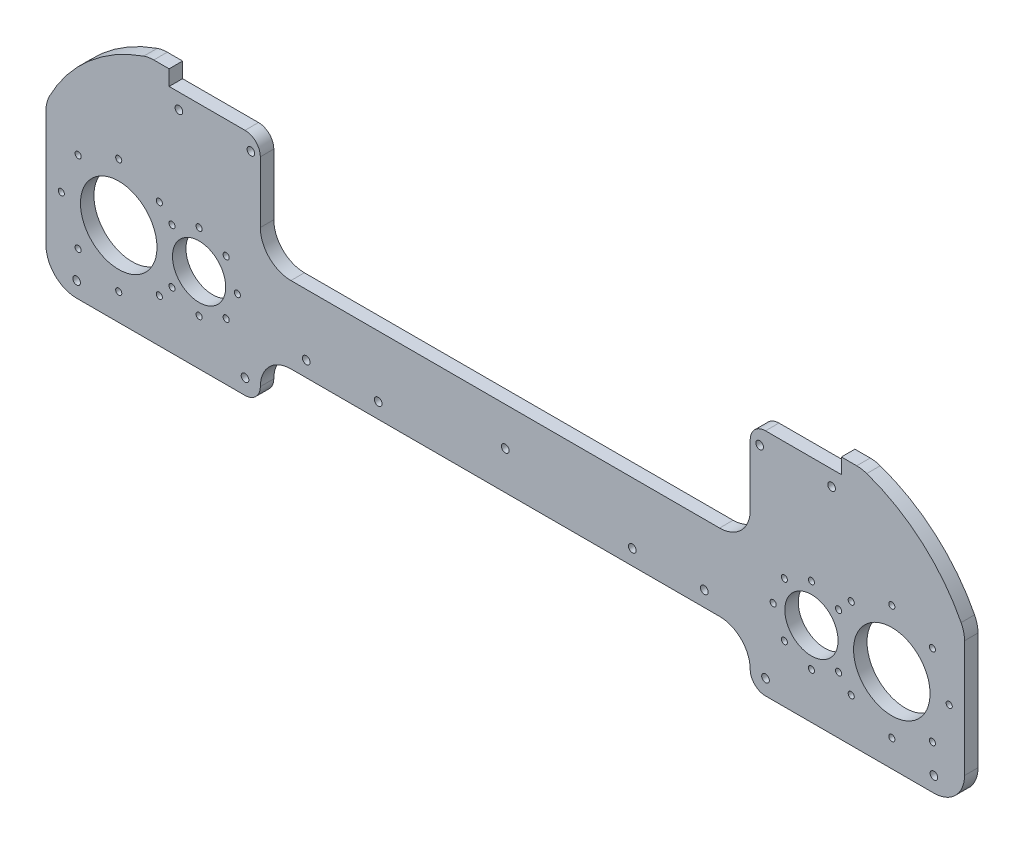
SolidWorks part; units mm, degrees
material "ABS"
ref_plane "Front Plane" through (0, 0, 0) normal (0, 0, 1) x (1, 0, 0)
ref_plane "Top Plane" through (0, 0, 0) normal (0, 1, 0) x (1, 0, 0)
ref_plane "Right Plane" through (0, 0, 0) normal (1, 0, 0) x (0, 0, -1)
sketch "Sketch1" plane through (0, 0, 0) normal (0, 0, 1) x (1, 0, 0)
  line L0 (-145.7836, 66.675) -> (145.7836, 66.675)
  line L1 (-190.5, 26.1817) -> (-190.5, -22.225)
  line L4 (0, 0) -> (0, 100.7987) construction
  line L5 (-177.8, -34.925) -> (177.8, -34.925)
  line L6 (190.5, 26.1817) -> (190.5, -22.225)
  line L7 (-190.5, 34.925) -> (190.5, -34.925) construction
  line L8 (-190.5, -34.925) -> (190.5, 34.925) construction
  arc A0 (177.8, -34.925) -> (190.5, -22.225) centre (177.8, -22.225) ccw
  arc A1 (149.9577, 65.9694) -> (189.0889, 31.9999) centre (127, 0) cw
  circle A2 centre (-127, 0) radius 3.175
  circle A3 centre (127, 0) radius 3.175
  arc A4 (-177.8, -34.925) -> (-190.5, -22.225) centre (-177.8, -22.225) cw
  arc A5 (190.5, 26.1817) -> (189.0889, 31.9999) centre (177.8, 26.1817) ccw
  arc A6 (-149.9577, 65.9694) -> (-189.0889, 31.9999) centre (-127, 0) ccw
  arc A7 (149.9577, 65.9694) -> (145.7836, 66.675) centre (145.7836, 53.975) ccw
  arc A8 (-190.5, 26.1817) -> (-189.0889, 31.9999) centre (-177.8, 26.1817) cw
  arc A9 (-145.7836, 66.675) -> (-149.9577, 65.9694) centre (-145.7836, 53.975) ccw
  point P0 (0, 0)
  point P22 (190.5, 29.0994)
  point P27 (147.8199, 66.675)
  point P30 (-190.5, 29.0994)
  point P33 (-147.8199, 66.675)
  dimension "D3" = 6.35
  dimension "D4" = 6.35
  dimension "D6" = 66.675
  dimension "D7" = 12.7
  dimension "D2" = 381
  dimension "D5" = 12.7
  dimension "D1" = 69.85
  dimension "D8" = 139.7
extrude "Boss-Extrude1" add sketch "Sketch1" along normal mid plane 5.588
sketch "Sketch2" plane through (0, 0, 2.794) normal (0, 0, 1) x (1, 0, 0)
  line L0 (-127, 0) -> (-207.737, 0) construction
  line L1 (127, 0) -> (207.737, 0) construction
  line L4 (0, 0) -> (0, 93.9723) construction
  circle A0 centre (-127, 0) radius 11.049
  circle A1 centre (-160.3375, 0) radius 15.875
  circle A2 centre (-143.4995, 16.838) radius 1.27
  circle A3 centre (-136.525, 0) radius 1.27 [skipped]
  circle A4 centre (-160.3375, 0) radius 23.8125 construction
  circle A5 centre (-127, 0) radius 15.875 construction
  circle A6 centre (-160.3375, 23.8125) radius 1.27
  circle A7 centre (-143.4995, -16.838) radius 1.27
  circle A8 centre (-160.3375, -23.8125) radius 1.27
  circle A9 centre (-177.1755, -16.838) radius 1.27
  circle A10 centre (-184.15, 0) radius 1.27
  circle A11 centre (-177.1755, 16.838) radius 1.27
  circle A12 centre (127, 0) radius 15.875 construction
  circle A13 centre (160.3375, 0) radius 23.8125 construction
  circle A14 centre (-127, 15.875) radius 1.27
  circle A15 centre (-115.7747, 11.2253) radius 1.27
  circle A16 centre (-111.125, 0) radius 1.27
  circle A17 centre (-115.7747, -11.2253) radius 1.27
  circle A18 centre (-127, -15.875) radius 1.27
  circle A19 centre (-138.2253, -11.2253) radius 1.27
  circle A20 centre (138.2253, 11.2253) radius 1.27
  circle A21 centre (-138.2253, 11.2253) radius 1.27
  circle A22 centre (-142.875, 0) radius 1.27 [skipped]
  circle A23 centre (138.2253, -11.2253) radius 1.27
  circle A24 centre (127, -15.875) radius 1.27
  circle A25 centre (115.7747, -11.2253) radius 1.27
  circle A26 centre (111.125, 0) radius 1.27
  circle A27 centre (115.7747, 11.2253) radius 1.27
  circle A28 centre (127, 15.875) radius 1.27
  circle A29 centre (177.1755, 16.838) radius 1.27
  circle A30 centre (184.15, 0) radius 1.27
  circle A31 centre (177.1755, -16.838) radius 1.27
  circle A32 centre (160.3375, -23.8125) radius 1.27
  circle A33 centre (143.4995, -16.838) radius 1.27
  circle A34 centre (160.3375, 23.8125) radius 1.27
  circle A35 centre (143.4995, 16.838) radius 1.27
  circle A36 centre (160.3375, 0) radius 15.875
  circle A37 centre (127, 0) radius 11.049
  dimension "D2" = 33.3375
  dimension "D3" = 31.75
  dimension "D4" = 31.75
  dimension "D5" = 47.625
  dimension "D6" = 2.54
  dimension "D1" = 22.098
  dimension "D8" = 2.54
  dimension "D7" = 8
  dimension "D9" = 8
extrude "Cut-Extrude1" cut sketch "Sketch2" against normal through all
sketch "Sketch5" plane through (0, 0, 2.794) normal (0, 0, 1) x (1, 0, 0)
  line L0 (145.7836, 66.675) -> (-145.7836, 66.675) construction
  line L1 (-88.9, 15.875) -> (88.9, 15.875)
  line L2 (-101.6, 28.575) -> (-101.6, 66.675)
  line L3 (-101.6, 66.675) -> (101.6, 66.675)
  line L4 (101.6, 28.575) -> (101.6, 66.675)
  line L5 (-101.6, 15.875) -> (101.6, 66.675) construction
  line L6 (-101.6, 66.675) -> (101.6, 15.875) construction
  line L7 (0, 0) -> (0, 128.2224) construction
  arc A0 (101.6, 28.575) -> (88.9, 15.875) centre (88.9, 28.575) cw
  arc A1 (-88.9, 15.875) -> (-101.6, 28.575) centre (-88.9, 28.575) cw
  point P0 (0, 41.275)
  dimension "D3" = 12.7
  dimension "D1" = 50.8
  dimension "D2" = 203.2
extrude "ITC_Cutout" cut sketch "Sketch5" against normal through all
sketch "Sketch6" plane through (0, 0, 2.794) normal (0, 0, 1) x (1, 0, 0)
  line L0 (-101.6, 66.675) -> (-145.7836, 66.675) construction
  line L1 (-71.9103, 66.675) -> (-139.4336, 66.675)
  line L2 (-71.9103, 66.675) -> (-71.9103, 60.325)
  line L3 (-71.9103, 60.325) -> (-139.4336, 60.325)
  line L4 (-139.4336, 66.675) -> (-139.4336, 60.325)
  line L5 (0, 0) -> (0, 132.6418) construction
  line L6 (139.4336, 66.675) -> (139.4336, 60.325)
  line L7 (71.9103, 60.325) -> (139.4336, 60.325)
  line L8 (71.9103, 66.675) -> (71.9103, 60.325)
  line L9 (71.9103, 66.675) -> (139.4336, 66.675)
  dimension "D1" = 6.35
  dimension "D2" = 6.35
extrude "Cut-Extrude3" cut sketch "Sketch6" against normal through all
fillet "Fillet1" radius 6.35 2 edges at (101.6, 60.325, 0) (-101.6, 60.325, 0)
sketch "Sketch7" plane through (0, 0, 2.794) normal (0, 0, 1) x (1, 0, 0)
  line L0 (0, 38.9819) -> (0, -79.3414) construction
  line L1 (-177.8, -34.925) -> (177.8, -34.925) construction
  line L2 (-88.9, -15.875) -> (88.9, -15.875)
  line L3 (-101.6, -28.575) -> (-101.6, -34.925)
  line L4 (-101.6, -34.925) -> (101.6, -34.925)
  line L5 (101.6, -28.575) -> (101.6, -34.925)
  line L6 (-101.6, -15.875) -> (101.6, -34.925) construction
  line L7 (-101.6, -34.925) -> (101.6, -15.875) construction
  line L8 (-101.6, 53.975) -> (-101.6, 28.575) construction
  arc A0 (101.6, -28.575) -> (88.9, -15.875) centre (88.9, -28.575) ccw
  arc A1 (-88.9, -15.875) -> (-101.6, -28.575) centre (-88.9, -28.575) ccw
  point P3 (0, -25.4)
  dimension "D2" = 12.7
  dimension "D1" = 19.05
extrude "Cut-Extrude4" cut sketch "Sketch7" against normal through all
fillet "Fillet2" radius 6.35 2 edges at (101.6, -34.925, 0) (-101.6, -34.925, 0)
sketch "Sketch8" plane through (0, 0, 2.794) normal (0, 0, 1) x (1, 0, 0)
  line L0 (-139.4336, 60.325) -> (-107.95, 60.325) construction
  line L1 (-139.4336, 66.675) -> (-139.4336, 60.325) construction
  line L2 (0, 0) -> (0, 74.8203) construction
  circle A0 centre (-135.3696, 53.975) radius 1.5875
  circle A1 centre (-105.5246, 53.975) radius 1.5875
  circle A2 centre (105.5246, 53.975) radius 1.5875
  circle A3 centre (135.3696, 53.975) radius 1.5875
  dimension "D1" = 3.175
  dimension "D3" = 3.175
  dimension "D2" = 6.35
  dimension "D4" = 29.845
  dimension "D5" = 4.064
extrude "Cut-Extrude5" cut sketch "Sketch8" against normal through all
sketch "Sketch10" plane through (0, 0, 2.794) normal (0, 0, 1) x (1, 0, 0)
  line L0 (0, 50.0636) -> (0, -61.6077) construction
  line L1 (-177.8, -34.925) -> (-107.95, -34.925) construction
  circle A0 centre (-177.8, -28.575) radius 1.5875
  circle A1 centre (-107.95, -28.575) radius 1.5875
  circle A2 centre (107.95, -28.575) radius 1.5875
  circle A3 centre (177.8, -28.575) radius 1.5875
  circle A4 centre (0, 0) radius 1.5875
  dimension "D1" = 3.175
  dimension "D4" = 3.175
  dimension "D6" = 3.175
  dimension "D2" = 6.35
  dimension "D3" = 177.8
  dimension "D5" = 107.95
extrude "Cut-Extrude6" cut sketch "Sketch10" against normal through all
sketch "Sketch11" plane through (0, 0, 2.794) normal (0, 0, 1) x (1, 0, 0)
  line L0 (0, 40.4641) -> (0, -48.1411) construction
  line L1 (88.9, -15.875) -> (-88.9, -15.875) construction
  circle A0 centre (-82.55, -9.525) radius 1.5875
  circle A1 centre (-52.705, -9.525) radius 1.5875
  circle A2 centre (52.705, -9.525) radius 1.5875
  circle A3 centre (82.55, -9.525) radius 1.5875
  dimension "D3" = 3.175
  dimension "D5" = 3.175
  dimension "D1" = 82.55
  dimension "D2" = 29.845
  dimension "D4" = 6.35
extrude "Cut-Extrude7" cut sketch "Sketch11" against normal through all
equation "\"D3@Sketch8\" = \"D1@Sketch8\""
